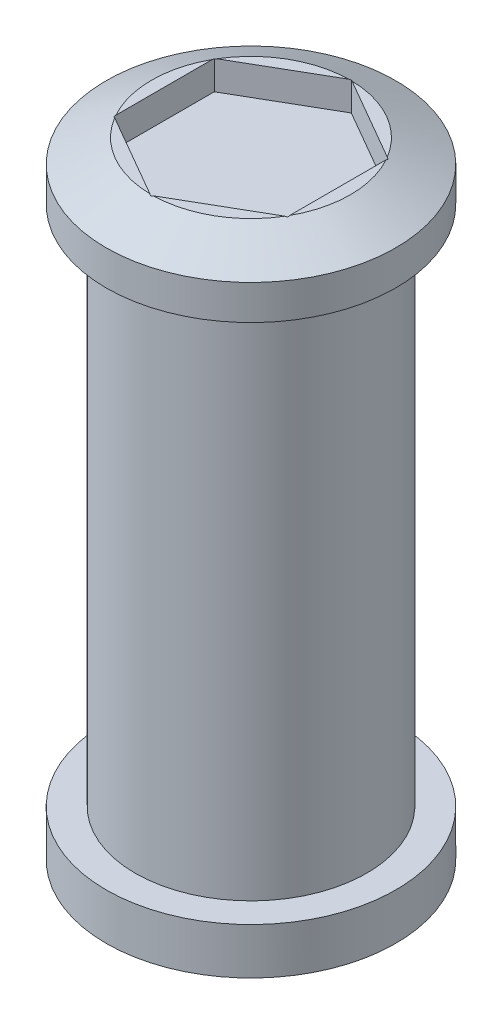
SolidWorks part; units mm, degrees
material "1060 Alloy"
ref_plane "Front Plane" through (0, 0, 0) normal (0, 0, 1) x (1, 0, 0)
ref_plane "Top Plane" through (0, 0, 0) normal (0, 1, 0) x (1, 0, 0)
ref_plane "Right Plane" through (0, 0, 0) normal (1, 0, 0) x (0, 0, -1)
sketch "Sketch1" plane through (0, 0, 0) normal (0, 1, 0) x (1, 0, 0)
  circle A0 centre (0, 0) radius 50.8
  dimension "D1" = 101.6
extrude "Boss-Extrude1" add sketch "Sketch1" along normal blind 228.6
sketch "Sketch2" plane through (0, 228.6, 0) normal (0, 1, 0) x (1, 0, 0)
  circle A0 centre (0, 0) radius 63.5
  dimension "D1" = 127
extrude "Boss-Extrude2" add sketch "Sketch2" along normal blind 25.4
sketch "Sketch3" plane through (0, 0, 0) normal (0, -1, 0) x (1, 0, 0)
  circle A0 centre (0, 0) radius 63.5
extrude "Boss-Extrude3" add sketch "Sketch3" along normal blind 25.4
sketch "Sketch4" plane through (0, 254, 0) normal (0, 1, 0) x (1, 0, 0)
  line L1 (0, 43.9941) -> (-38.1, 21.997)
  line L2 (-38.1, 21.997) -> (-38.1, -21.997)
  line L3 (-38.1, -21.997) -> (0, -43.9941)
  line L4 (0, -43.9941) -> (38.1, -21.997)
  line L5 (38.1, -21.997) -> (38.1, 21.997)
  line L6 (38.1, 21.997) -> (0, 43.9941)
  circle A0 centre (0, 0) radius 38.1 construction
  dimension "D1" = 76.2
extrude "Cut-Extrude2" cut sketch "Sketch4" against normal blind 12.7
chamfer "Chamfer2" distance 10.16 angle 63 1 edges at (0, 254, 63.5) first distance on face at (0, 254, 63.5)
sketch "Sketch5" plane through (0, -25.4, 0) normal (0, -1, 0) x (1, 0, 0)
  line L1 (0, 43.9941) -> (-38.1, 21.997)
  line L2 (-38.1, 21.997) -> (-38.1, -21.997)
  line L3 (-38.1, -21.997) -> (0, -43.9941)
  line L4 (0, -43.9941) -> (38.1, -21.997)
  line L5 (38.1, -21.997) -> (38.1, 21.997)
  line L6 (38.1, 21.997) -> (0, 43.9941)
  circle A0 centre (0, 0) radius 38.1
  dimension "D1" = 76.2
extrude "Cut-Extrude5" cut sketch "Sketch5" against normal blind 12.7 contours A0 | A0 L6 L1 | A0 L5 L6 | A0 L1 L2 | A0 L2 L3 | A0 L4 L5 | A0 L3 L4 region at (0, -25.4, 39.3788) region at (-34.103, -25.4, 19.6894) region at (0, -25.4, 0) region at (34.103, -25.4, 19.6894) region at (-34.103, -25.4, -19.6894) region at (34.103, -25.4, -19.6894) region at (0, -25.4, -39.3788)
chamfer "Chamfer3" distance 5.08 angle 74 1 edges at (0, -25.4, -63.5) first distance on face at (0, -25.4, -63.5)
sketch "Sketch6" plane through (0, -12.7, 0) normal (0, -1, 0) x (1, 0, 0)
  circle A0 centre (0, 0) radius 31.75
  dimension "D1" = 63.5
extrude "Boss-Extrude6" add sketch "Sketch6" along normal blind 12.7
